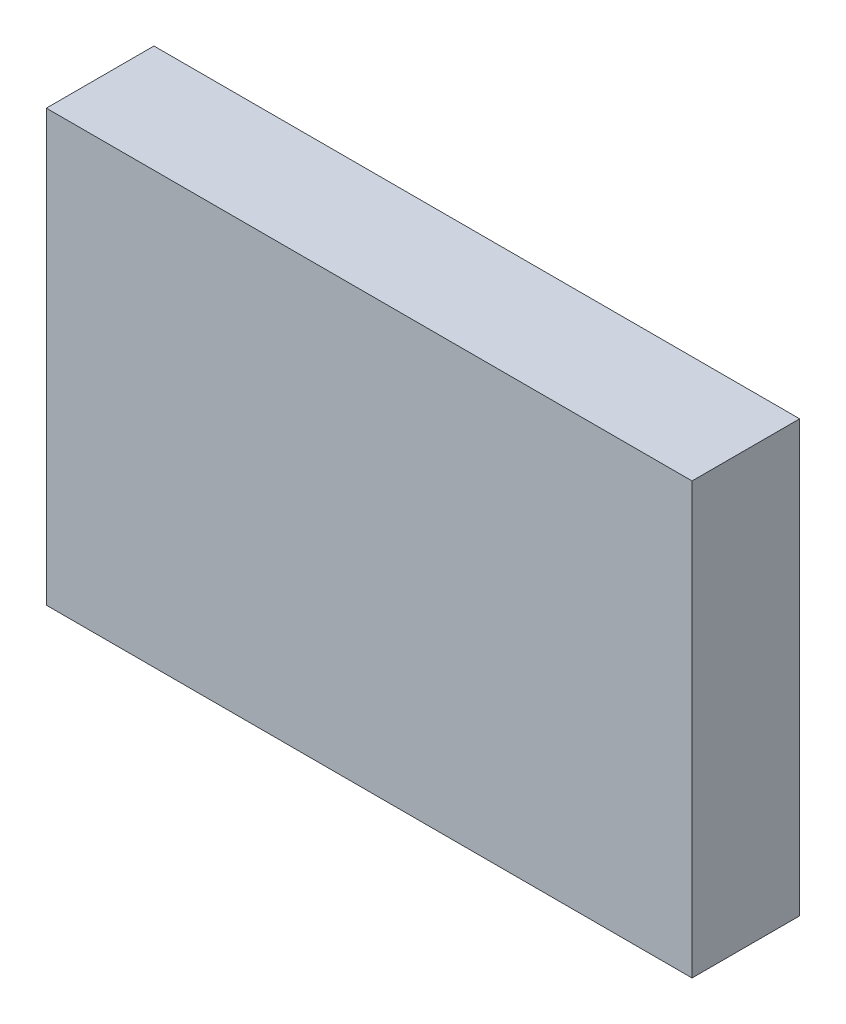
SolidWorks part; units mm, degrees
ref_plane "Přední rovina" through (0, 0, 0) normal (0, 0, 1) x (1, 0, 0)
ref_plane "Horní rovina" through (0, 0, 0) normal (0, 1, 0) x (1, 0, 0)
ref_plane "Pravá rovina" through (0, 0, 0) normal (1, 0, 0) x (0, 0, -1)
ref_plane "Plane2" through (0, 0, 20) normal (0, 0, 1) x (1, 0, 0)
sketch "Sketch3" plane through (0, 0, 20) normal (0, 0, 1) x (1, 0, 0)
  line L1 (15, -10) -> (-15, -10)
  line L2 (15, -10) -> (15, 10)
  line L3 (15, 10) -> (-15, 10)
  line L4 (-15, -10) -> (-15, 10)
  line L5 (15, -10) -> (-15, 10) construction
  line L6 (15, 10) -> (-15, -10) construction
  point P0 (0, 0)
  dimension "D1" = 30
  dimension "D2" = 20
extrude "Boss-Extrude1" add sketch "Sketch3" along normal blind 5
sketch "Sketch7" plane through (0, 10, 0) normal (0, 1, 0) x (1, 0, 0)
  line L0 (15, -25) -> (15, -20)
  line L1 (15, -25) -> (-15.5788, -25)
  line L2 (15, -20) -> (-15.5788, -20)
  line L3 (-15.5788, -25) -> (-15.5788, -20)
equation "\"SH\"= 3mm"
equation "\"OH\"= 5mm"
equation "\"D1@Boss-Extrude1\"=\"OH\""
